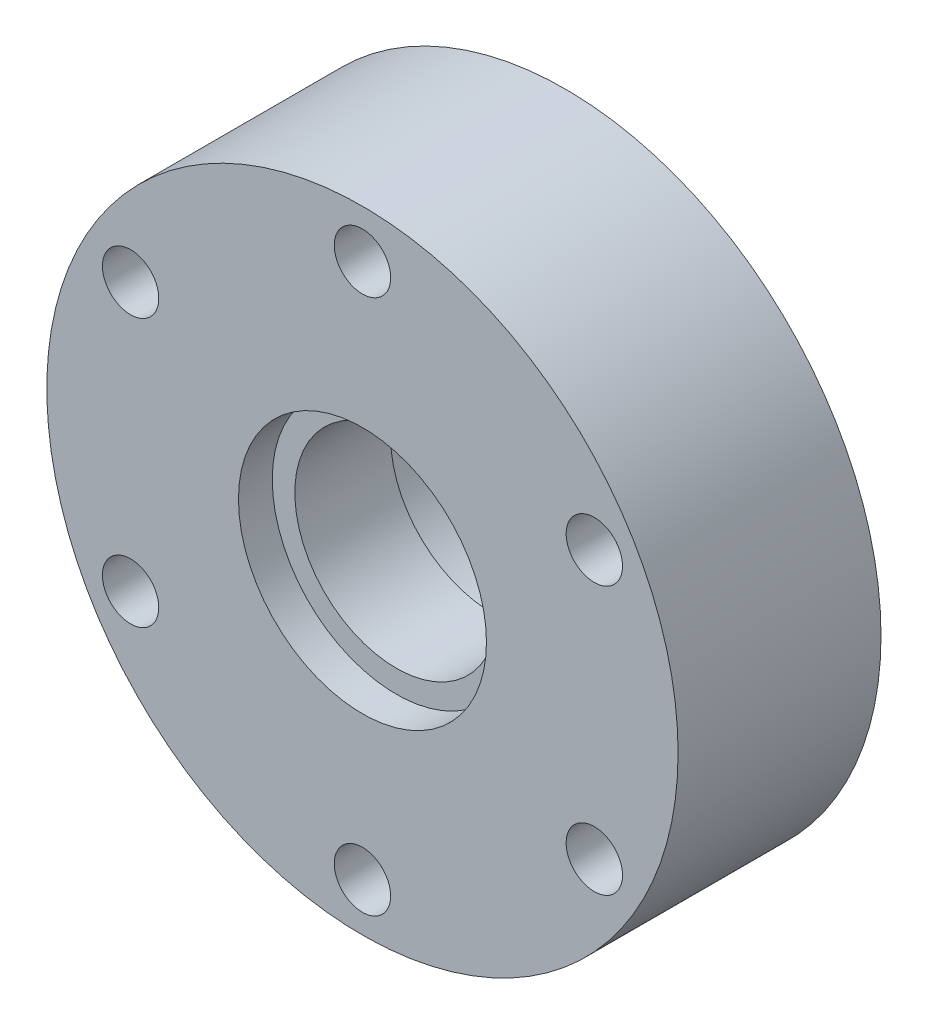
SolidWorks part; units mm, degrees
material "Polybutadiene (PB)"
ref_plane "Front Plane" through (0, 0, 0) normal (0, 0, 1) x (1, 0, 0)
ref_plane "Top Plane" through (0, 0, 0) normal (0, 1, 0) x (1, 0, 0)
ref_plane "Right Plane" through (0, 0, 0) normal (1, 0, 0) x (0, 0, -1)
sketch "Sketch1" plane through (0, 0, 0) normal (0, 0, 1) x (1, 0, 0)
  circle A0 centre (0, 0) radius 28
  dimension "D1" = 56
extrude "Boss-Extrude1" add sketch "Sketch1" along normal mid plane 18
sketch "Sketch2" plane through (0, 0, 9) normal (0, 0, 1) x (1, 0, 0)
  circle A0 centre (0, 0) radius 11
extrude "Cut-Extrude1" cut sketch "Sketch2" against normal blind 3
sketch "Sketch3" plane through (0, 0, 6) normal (0, 0, 1) x (1, 0, 0)
  circle A0 centre (0, 0) radius 9
extrude "Cut-Extrude2" cut sketch "Sketch3" against normal through all
sketch "Sketch4" plane through (0, 0, -9) normal (0, 0, -1) x (-1, 0, 0)
  circle A0 centre (0, 0) radius 11
extrude "Cut-Extrude3" cut sketch "Sketch4" against normal blind 6.5
sketch "草圖1" plane through (0, 0, 9) normal (0, 0, 1) x (1, 0, 0)
  line L0 (0, 0) -> (0, 23.75) construction
  circle A0 centre (0, 23.75) radius 2.5
  dimension "D1" = 5
  dimension "D2" = 23.75
extrude "除料-伸長1" cut sketch "草圖1" against normal through all
pattern_circular "環狀複製排列1" count 6 over 360 about axis through (0, 0, 9) along (0, 0, 1) of "除料-伸長1"
